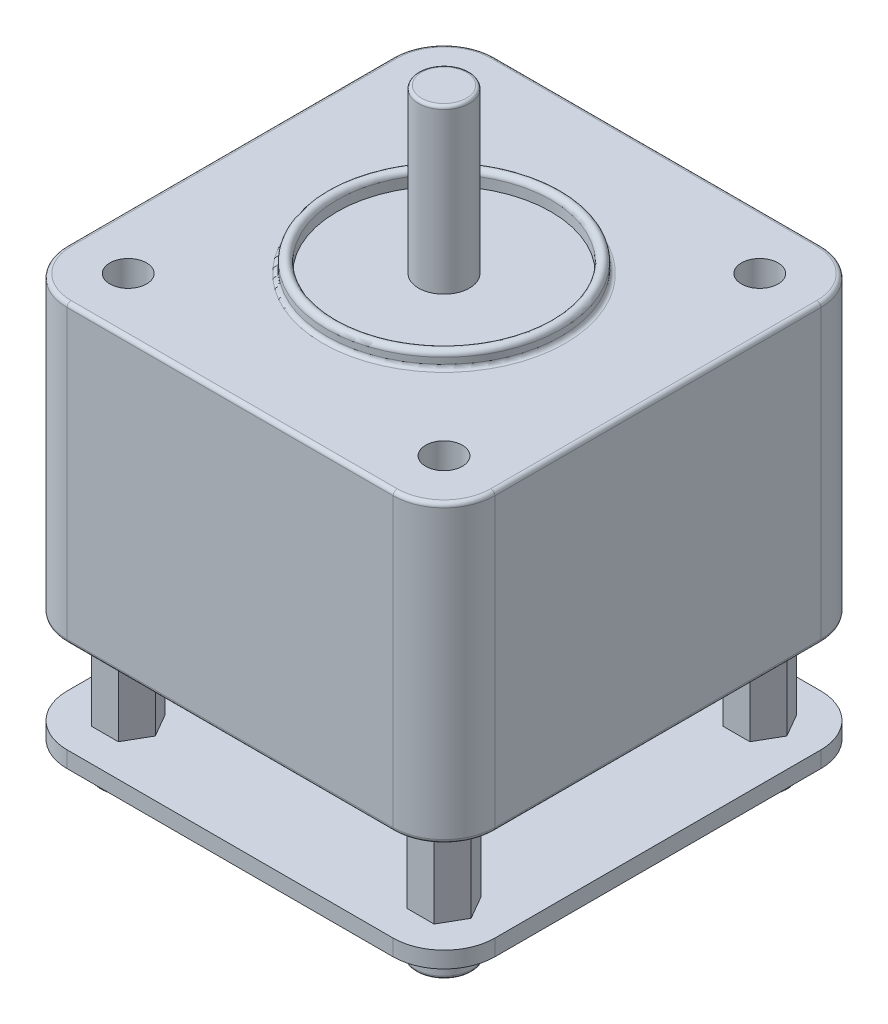
SolidWorks part; units mm, degrees
ref_plane "前视基准面" through (0, 0, 0) normal (0, 0, 1) x (1, 0, 0)
ref_plane "上视基准面" through (0, 0, 0) normal (0, 1, 0) x (1, 0, 0)
ref_plane "右视基准面" through (0, 0, 0) normal (1, 0, 0) x (0, 0, -1)
sketch "草图1" plane through (0, 0, 0) normal (0, 1, 0) x (1, 0, 0)
  line L1 (-21, 21) -> (21, 21)
  line L2 (-21, 21) -> (-21, -21)
  line L3 (-21, -21) -> (21, -21)
  line L4 (21, 21) -> (21, -21)
  line L5 (-21, 21) -> (21, -21) construction
  line L6 (-21, -21) -> (21, 21) construction
  point P0 (0, 0)
  dimension "D1" = 42
  dimension "D2" = 42
extrude "凸台-拉伸1" add sketch "草图1" along normal blind 29
sketch "草图2" plane through (0, 29, 0) normal (0, 1, 0) x (1, 0, 0)
  circle A0 centre (0, 0) radius 11.5
  circle A1 centre (0, 0) radius 10.5
  circle A2 centre (0, 0) radius 2.5
  dimension "D1" = 23
  dimension "D2" = 1
  dimension "D3" = 5
extrude "凸台-拉伸2" add sketch "草图2" along normal blind 2 contours A0 A1 region at (-11.1747, 29, 0)
extrude "凸台-拉伸3" add sketch "草图2<3>" along normal blind 16 contours A2 region at (0, 29, 0)
sketch "草图2<3>" plane through (0, 29, 0) normal (0, 1, 0) x (1, 0, 0) same geometry as "草图2"
sketch "草图4" plane through (0, 29, 0) normal (0, 1, 0) x (1, 0, 0)
  line L0 (21, 21) -> (-21, 21) construction
  line L1 (-21, 21) -> (-21, -21) construction
  line L2 (0, -17.05) -> (0, 17.05) construction
  line L3 (-17.05, 0) -> (17.05, 0) construction
  circle A0 centre (-15.5, 15.5) radius 1.8
  circle A1 centre (15.5, 15.5) radius 1.8
  circle A2 centre (15.5, -15.5) radius 1.8
  circle A3 centre (-15.5, -15.5) radius 1.8
  dimension "D1" = 3.6
  dimension "D3" = 5.5
  dimension "D2" = 5.5
extrude "切除-拉伸1" cut sketch "草图4" against normal through all
sketch "草图5" plane through (0, 0, 0) normal (0, -1, 0) x (1, 0, 0)
  line L0 (17.05, 0) -> (-17.05, 0) construction
  line L1 (-14.1721, 13.2) -> (-12.8442, 15.5)
  line L2 (-12.8442, 15.5) -> (-14.1721, 17.8)
  line L3 (-14.1721, 17.8) -> (-16.8279, 17.8)
  line L4 (-16.8279, 17.8) -> (-18.1558, 15.5)
  line L5 (-18.1558, 15.5) -> (-16.8279, 13.2)
  line L6 (-16.8279, 13.2) -> (-14.1721, 13.2)
  line L7 (-16.8279, -13.2) -> (-14.1721, -13.2)
  line L8 (-18.1558, -15.5) -> (-16.8279, -13.2)
  line L9 (-16.8279, -17.8) -> (-18.1558, -15.5)
  line L10 (-14.1721, -17.8) -> (-16.8279, -17.8)
  line L11 (-12.8442, -15.5) -> (-14.1721, -17.8)
  line L12 (-14.1721, -13.2) -> (-12.8442, -15.5)
  line L13 (0, -17.05) -> (0, 17.05) construction
  line L14 (18.1558, -15.5) -> (16.8279, -13.2)
  line L15 (16.8279, -17.8) -> (18.1558, -15.5)
  line L16 (14.1721, -17.8) -> (16.8279, -17.8)
  line L17 (12.8442, -15.5) -> (14.1721, -17.8)
  line L18 (14.1721, -13.2) -> (12.8442, -15.5)
  line L19 (16.8279, -13.2) -> (14.1721, -13.2)
  line L20 (16.8279, 13.2) -> (14.1721, 13.2)
  line L21 (18.1558, 15.5) -> (16.8279, 13.2)
  line L22 (16.8279, 17.8) -> (18.1558, 15.5)
  line L23 (14.1721, 17.8) -> (16.8279, 17.8)
  line L24 (12.8442, 15.5) -> (14.1721, 17.8)
  line L25 (14.1721, 13.2) -> (12.8442, 15.5)
  circle A0 centre (-15.5, 15.5) radius 2.3 construction
  dimension "D1" = 4.6
extrude "凸台-拉伸4" add sketch "草图5" along normal blind 9
sketch "草图6" plane through (0, -9, 0) normal (0, -1, 0) x (1, 0, 0)
  line L1 (-21, 21) -> (21, 21)
  line L2 (-21, 21) -> (-21, -21)
  line L3 (-21, -21) -> (21, -21)
  line L4 (21, 21) -> (21, -21)
  line L5 (-21, 21) -> (21, -21) construction
  line L6 (-21, -21) -> (21, 21) construction
  point P0 (0, 0)
extrude "凸台-拉伸5" add sketch "草图6" along normal blind 1.6
sketch "草图7" plane through (0, -10.6, 0) normal (0, -1, 0) x (1, 0, 0)
  line L0 (16.2217, 14.25) -> (16.9434, 15.5)
  line L1 (-14.7783, 14.25) -> (-14.0566, 15.5)
  line L2 (-14.0566, 15.5) -> (-14.7783, 16.75)
  line L3 (-14.7783, 16.75) -> (-16.2217, 16.75)
  line L4 (-16.2217, 16.75) -> (-16.9434, 15.5)
  line L5 (-16.9434, 15.5) -> (-16.2217, 14.25)
  line L6 (-16.2217, 14.25) -> (-14.7783, 14.25)
  line L7 (16.9434, 15.5) -> (16.2217, 16.75)
  line L8 (16.2217, 16.75) -> (14.7783, 16.75)
  line L9 (14.7783, 16.75) -> (14.0566, 15.5)
  line L10 (14.0566, 15.5) -> (14.7783, 14.25)
  line L11 (14.7783, 14.25) -> (16.2217, 14.25)
  line L12 (16.2217, -16.75) -> (16.9434, -15.5)
  line L13 (16.9434, -15.5) -> (16.2217, -14.25)
  line L14 (16.2217, -14.25) -> (14.7783, -14.25)
  line L15 (14.7783, -14.25) -> (14.0566, -15.5)
  line L16 (14.0566, -15.5) -> (14.7783, -16.75)
  line L17 (14.7783, -16.75) -> (16.2217, -16.75)
  line L18 (-14.7783, -16.75) -> (-14.0566, -15.5)
  line L19 (-14.0566, -15.5) -> (-14.7783, -14.25)
  line L20 (-14.7783, -14.25) -> (-16.2217, -14.25)
  line L21 (-16.2217, -14.25) -> (-16.9434, -15.5)
  line L22 (-16.9434, -15.5) -> (-16.2217, -16.75)
  line L23 (-16.2217, -16.75) -> (-14.7783, -16.75)
  line L25 (21, -21) -> (-21, -21) construction
  line L28 (21, -21) -> (21, 21) construction
  circle A0 centre (-15.5, 15.5) radius 2.75
  circle A1 centre (-15.5, 15.5) radius 1.25 construction
  circle A2 centre (15.5, 15.5) radius 2.75
  circle A3 centre (15.5, 15.5) radius 1.25 construction
  circle A4 centre (15.5, -15.5) radius 2.75
  circle A5 centre (15.5, -15.5) radius 1.25 construction
  circle A6 centre (-15.5, -15.5) radius 2.75
  circle A7 centre (-15.5, -15.5) radius 1.25 construction
  dimension "D2" = 5.5
  dimension "D1" = 2.5
  dimension "D5" = 5.5
  dimension "D6" = 5.5
  dimension "D3" = 2
  dimension "D4" = 2
extrude "凸台-拉伸6" add sketch "草图7" along direction (0, -1, 0) on the side of the normal blind 3
fillet "圆角1" radius 5 8 edges at (-21, 14.5, -21) (-21, 14.5, 21) (21, 14.5, 21) (21, 14.5, -21) (-21, -9.8, 21) (21, -9.8, 21) (21, -9.8, -21) (-21, -9.8, -21)
fillet "圆角2" radius 1 1 edges at (0, 31, 11.5)
fillet "圆角3" radius 0.5 1 edges at (0, 31, 10.5)
fillet "圆角4" radius 0.4 1 edges at (0, 29, 11.5)
fillet "圆角5" radius 0.4 16 edges at (0, 29, -21) (19.5355, 29, -19.5355) (21, 29, 0) (19.5355, 29, 19.5355) (0, 29, 21) (-19.5355, 29, 19.5355) (-21, 29, 0) (-19.5355, 29, -19.5355) (19.5355, 0, -19.5355) (21, 0, 0) (19.5355, 0, 19.5355) (0, 0, 21) (-19.5355, 0, 19.5355) (-21, 0, 0) (-19.5355, 0, -19.5355) (0, 0, -21)
fillet "圆角6" radius 0.3 4 edges at (15.5, -13.6, 12.75) (15.5, -13.6, -18.25) (-15.5, -13.6, -18.25) (-15.5, -13.6, 12.75)
fillet "圆角7" radius 0.3 1 edges at (0, 45, 2.5)
